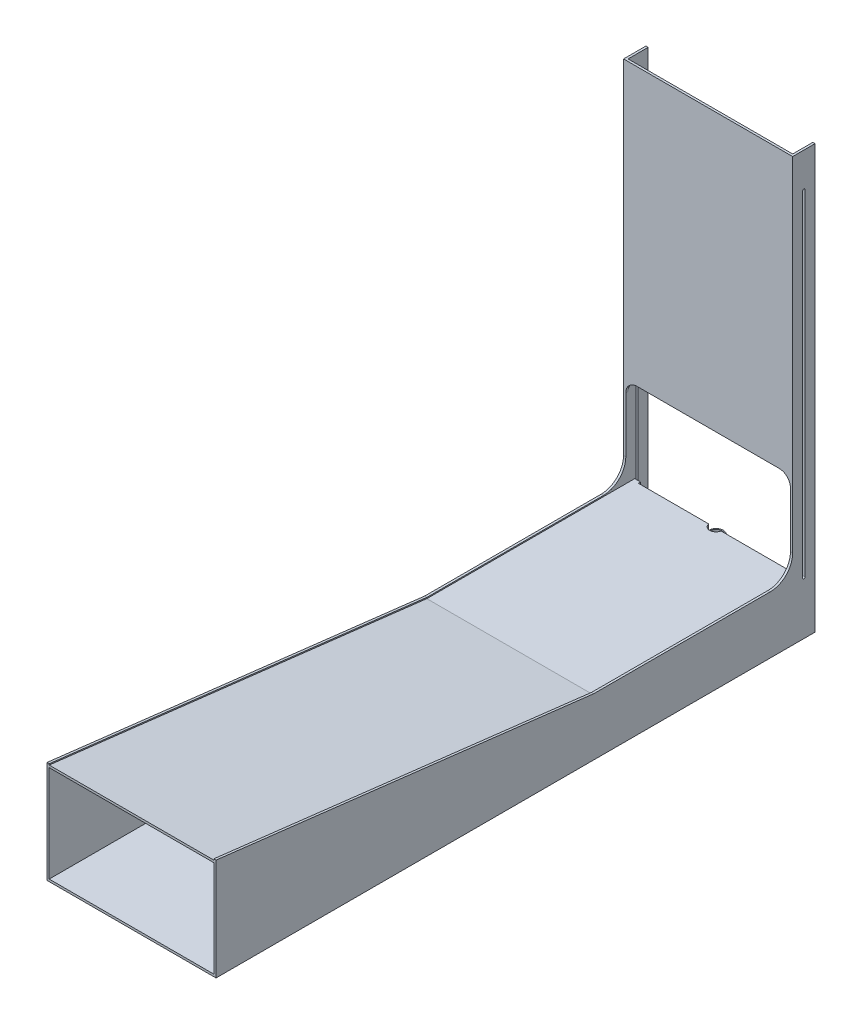
SolidWorks part; units mm, degrees
material "AISI 4340 Steel, annealed"
ref_plane "Front Plane" through (0, 0, 0) normal (0, 0, 1) x (1, 0, 0)
ref_plane "Top Plane" through (0, 0, 0) normal (0, 1, 0) x (1, 0, 0)
ref_plane "Right Plane" through (0, 0, 0) normal (1, 0, 0) x (0, 0, -1)
ref_plane "Right side of elevator platform" through (368, 0, 0) normal (1, 0, 0) x (0, 0, -1)
sketch "Sketch2" plane through (368, 0, 0) normal (1, 0, 0) x (0, 0, -1)
  line L0 (50, 236.5) -> (50, 1736.5) construction
  line L1 (45, 236.5) -> (45, 1736.5)
  line L2 (55, 236.5) -> (55, 1736.5)
  line L4 (0, 0) -> (100, 0)
  line L5 (0, 0) -> (0, 1800)
  line L6 (0, 1800) -> (100, 1800)
  line L7 (100, 0) -> (100, 1800)
  arc A0 (45, 236.5) -> (55, 236.5) centre (50, 236.5) ccw
  arc A1 (55, 1736.5) -> (45, 1736.5) centre (50, 1736.5) ccw
  point P2 (50, 986.5)
  dimension "D6" = 5
  dimension "D1" = 1800
  dimension "D2" = 100
  dimension "D3" = 50
  dimension "D4" = 236.5
  dimension "D5" = 63.5
extrude "Right side guide" add sketch "Sketch2" along normal blind 10
sketch "Sketch3" plane through (368, 0, 0) normal (-1, 0, 0) x (0, 0, 1)
  line L0 (0, 1800) -> (0, 0) construction
  line L1 (-100, 0) -> (0, 0)
  line L2 (-100, 0) -> (-100, 10)
  line L3 (-100, 10) -> (0, 10)
  line L4 (0, 0) -> (0, 10)
  dimension "D1" = 10
extrude "Bottom connection" add sketch "Sketch3" along normal blind 736
sketch "Sketch4" plane through (-368, 0, 0) normal (-1, 0, 0) x (0, 0, 1)
  line L0 (-55, 236.5) -> (-55, 1736.5) construction
  line L1 (-45, 1736.5) -> (-45, 236.5) construction
  line L2 (-55, 236.5) -> (-55, 1736.5)
  line L3 (-45, 1736.5) -> (-45, 236.5)
  line L4 (-100, 10) -> (0, 10)
  line L5 (0, 10) -> (0, 1800)
  line L6 (0, 1800) -> (-100, 1800)
  line L7 (-100, 1800) -> (-100, 10)
  line L9 (0, 10) -> (0, 1800)
  line L10 (0, 1800) -> (-100, 1800)
  line L11 (-100, 1800) -> (-100, 10)
  line L16 (-100, 10) -> (-100, 0)
  line L17 (-100, 0) -> (0, 0)
  line L18 (0, 0) -> (0, 10)
  line L19 (0, 10) -> (-100, 10)
  line L20 (-100, 10) -> (-100, 0)
  line L21 (-100, 0) -> (0, 0)
  line L22 (0, 0) -> (0, 10)
  arc A0 (-45, 1736.5) -> (-55, 1736.5) centre (-50, 1736.5) ccw construction
  arc A1 (-55, 236.5) -> (-45, 236.5) centre (-50, 236.5) ccw construction
  arc A2 (-45, 1736.5) -> (-55, 1736.5) centre (-50, 1736.5) ccw
  arc A3 (-55, 236.5) -> (-45, 236.5) centre (-50, 236.5) ccw
  dimension "D1" = 0
  dimension "D2" = 0
extrude "Left side guide" add sketch "Sketch4" along normal blind 10
sketch "Sketch5" plane through (0, 0, 0) normal (0, 0, 1) x (1, 0, 0)
  line L0 (-368, 10) -> (-368, 1800) construction
  line L1 (-368, 1800) -> (368, 1800)
  line L2 (-368, 1800) -> (-368, 653.8)
  line L3 (-368, 653.8) -> (368, 653.8)
  line L4 (368, 1800) -> (368, 653.8)
  line L5 (368, 1800) -> (368, 10) construction
  line L6 (378, 1800) -> (368, 1800) construction
  line L7 (-368, 10) -> (368, 10) construction
  dimension "D1" = 643.8
extrude "Structural webbing extrude" add sketch "Sketch5" against normal blind 10
sketch "Sketch6" plane through (0, 0, 0) normal (0, 0, 1) x (1, 0, 0)
  line L0 (-378, 251.5) -> (-378, 0)
  line L1 (-378, 0) -> (-378, 1800) construction
  line L2 (-378, 0) -> (378, 0)
  line L3 (378, 0) -> (378, 251.5)
  line L4 (378, 1800) -> (378, 0) construction
  line L5 (378, 251.5) -> (368, 251.5)
  line L6 (368, 653.8) -> (368, 10) construction
  line L7 (368, 251.5) -> (368, 10)
  line L8 (368, 10) -> (-368, 10)
  line L9 (-368, 10) -> (-368, 251.5)
  line L10 (-368, 10) -> (-368, 653.8) construction
  line L11 (-368, 251.5) -> (-378, 251.5)
  dimension "D1" = 241.5
extrude "Input roller holder extrude" add sketch "Sketch6" along normal blind 452.52
sketch "Sketch7" plane through (368, 0, 0) normal (-1, 0, 0) x (0, 0, 1)
  line L0 (0, 653.8) -> (0, 251.5) construction
  line L1 (452.52, 251.5) -> (-40, 251.5)
  line L2 (452.52, 251.5) -> (452.52, 241.5)
  line L3 (452.52, 241.5) -> (-40, 241.5)
  line L4 (-40, 251.5) -> (-40, 241.5)
  dimension "D1" = 40
  dimension "D2" = 10
extrude "Input roller platform" add sketch "Sketch7" along normal up to next
sketch "Sketch8" plane through (0, 251.5, 0) normal (0, 1, 0) x (1, 0, 0)
  line L1 (-378, -452.52) -> (-368, -452.52)
  line L2 (-378, -452.52) -> (-378, 0)
  line L3 (-378, 0) -> (-368, 0)
  line L4 (-368, -452.52) -> (-368, 0)
  line L5 (368, 0) -> (378, 0)
  line L6 (368, 0) -> (368, -452.52)
  line L7 (368, -452.52) -> (378, -452.52)
  line L8 (378, 0) -> (378, -452.52)
extrude "Siding outline" add sketch "Sketch8" along normal blind 5
sketch "Sketch9" plane through (0, 1800, 0) normal (0, 1, 0) x (1, 0, 0)
  line L8 (368, 100) -> (368, 10)
  line L9 (368, 10) -> (-368, 10)
  line L10 (-368, 10) -> (-368, 100)
  line L11 (-368, 100) -> (-378, 100)
  line L12 (-378, 100) -> (-378, 0)
  line L13 (-378, 0) -> (378, 0)
  line L14 (378, 0) -> (378, 100)
  line L15 (378, 100) -> (368, 100)
  line L16 (368, 100) -> (368, 10)
  line L17 (368, 10) -> (-368, 10)
  line L18 (-368, 10) -> (-368, 100)
  line L19 (-368, 100) -> (-378, 100)
  line L20 (-378, 100) -> (-378, 0)
  line L21 (-378, 0) -> (378, 0)
  line L22 (378, 0) -> (378, 100)
  line L23 (378, 100) -> (368, 100)
  dimension "D1" = 0
extrude "Lip to prevent box from falling out" add sketch "Sketch9" along normal blind 91.5
fillet "Vertical section fillets" radius 100 2 edges at (373, 256.5, 0) (-373, 256.5, 0)
fillet "Smaller fillets" radius 50 2 edges at (368, 653.8, -5) (-368, 653.8, -5)
sketch "Sketch11" plane through (0, 0, -40) normal (0, 0, -1) x (-1, 0, 0)
  line L0 (368, 251.5) -> (-368, 251.5) construction
  line L1 (-343, 251.5) -> (343, 251.5)
  line L2 (-343, 251.5) -> (-343, 241.5)
  line L3 (-343, 241.5) -> (343, 241.5)
  line L4 (343, 251.5) -> (343, 241.5)
  line L5 (368, 241.5) -> (-368, 241.5) construction
  line L6 (-368, 251.5) -> (-368, 241.5) construction
  line L7 (368, 251.5) -> (368, 241.5) construction
  dimension "D1" = 25
  dimension "D2" = 25
extrude "Gate spacing cut" cut sketch "Sketch11" against normal blind 10
sketch "Sketch12" plane through (-368, 0, 0) normal (1, 0, 0) x (0, 0, -1)
  line L1 (45, 221.5) -> (40, 221.5)
  line L2 (45, 221.5) -> (45, 10)
  line L3 (45, 10) -> (40, 10)
  line L4 (40, 221.5) -> (40, 10)
  line L5 (100, 1891.5) -> (100, 10) construction
  line L6 (45, 236.5) -> (45, 1736.5) construction
  line L7 (-452.52, 10) -> (100, 10) construction
  line L8 (40, 241.5) -> (-452.52, 241.5) construction
  line L9 (30, 241.5) -> (25, 241.5)
  line L10 (30, 241.5) -> (30, 10)
  line L11 (30, 10) -> (25, 10)
  line L12 (25, 241.5) -> (25, 10)
  dimension "D1" = 60
  dimension "D2" = 20
  dimension "D3" = 5
extrude "Gate guide rails" add sketch "Sketch12" along normal up to next
sketch "Sketch13" plane through (0, 0, -45) normal (0, 0, -1) x (-1, 0, 0)
  line L0 (-368, 221.5) -> (368, 221.5) construction
  line L1 (-328, 221.5) -> (328, 221.5)
  line L2 (-328, 221.5) -> (-328, 10)
  line L3 (-328, 10) -> (328, 10)
  line L4 (328, 221.5) -> (328, 10)
  line L5 (368, 10) -> (-368, 10) construction
  line L6 (-368, 10) -> (-368, 1891.5) construction
  point P8 (0, 221.5)
  dimension "D1" = 40
extrude "Gate rod connection cutout" cut sketch "Sketch13" against normal through all
sketch "Sketch14" plane through (0, 10, 0) normal (0, 1, 0) x (1, 0, 0)
  line L0 (328, 45) -> (-328, 25) construction
  circle A0 centre (0, 35) radius 28
  circle A1 centre (0, 35) radius 33
  point P7 (0, 35)
  dimension "D1" = 56
  dimension "D2" = 5
extrude "Spring cup" add sketch "Sketch14" along normal blind 75
sketch "Sketch15" plane through (0, 85, 0) normal (0, 1, 0) x (1, 0, 0)
  line L0 (368, 30) -> (328, 30) construction
  line L1 (32.619, 30) -> (27.55, 30)
  line L3 (32.619, 40) -> (27.55, 40)
  line L5 (-27.55, 40) -> (-32.619, 40)
  line L6 (-27.55, 30) -> (-32.619, 30)
  circle A0 centre (0, 35) radius 28 construction
  arc A1 (27.55, 40) -> (-27.55, 40) centre (0, 35) ccw
  circle A2 centre (0, 35) radius 33 construction
  arc A3 (32.619, 40) -> (-32.619, 40) centre (0, 35) ccw
  arc A4 (-27.55, 30) -> (27.55, 30) centre (0, 35) ccw
  arc A5 (-32.619, 30) -> (32.619, 30) centre (0, 35) ccw
extrude "Spring container extension" add sketch "Sketch15" along normal up to surface (136.5 mm away) up to face at (0, 221.5, -27.5)
sketch "Sketch16" plane through (0, 221.5, 0) normal (0, 1, 0) x (1, 0, 0)
  circle A0 centre (0, 35) radius 28
  arc A1 (27.55, 40) -> (-27.55, 40) centre (0, 35) ccw construction
extrude "Spring hole (can't insert spring without this)" cut sketch "Sketch16" along normal up to surface (30 mm away) up to face at (0, 251.5, 85.63)
sketch "Sketch17" plane through (0, 221.5, 0) normal (0, 1, 0) x (1, 0, 0)
  line L2 (-26.1534, 25) -> (-31.4484, 25)
  line L3 (31.4484, 25) -> (26.1534, 25)
  line L4 (-26.1534, 25) -> (-31.4484, 25)
  line L5 (31.4484, 25) -> (26.1534, 25)
  arc A2 (-31.4484, 25) -> (31.4484, 25) centre (0, 35) ccw
  arc A3 (-26.1534, 25) -> (26.1534, 25) centre (0, 35) ccw
  arc A4 (-31.4484, 25) -> (31.4484, 25) centre (0, 35) ccw
  arc A5 (-26.1534, 25) -> (26.1534, 25) centre (0, 35) ccw
  dimension "D1" = 0
extrude "Container extension to meet with conveyor plate" add sketch "Sketch17" along normal up to next
fillet "Spring holder fillets" radius 10 4 edges at (0, 10, -68) (-31.4484, 231.5, -25) (31.4484, 231.5, -25) (0, 241.5, -2)
sketch "Sketch18" plane through (0, 0, 452.52) normal (0, 0, 1) x (1, 0, 0)
  line L0 (368, 10) -> (368, 241.5) construction
  line L1 (-368, 241.5) -> (-368, 10) construction
  line L2 (368, 10) -> (368, 241.5)
  line L3 (-368, 241.5) -> (-368, 10)
  line L4 (-368, 241.5) -> (368, 241.5)
  line L5 (368, 10) -> (-368, 10)
  line L8 (378, 0) -> (378, 256.5)
  line L9 (378, 256.5) -> (368, 256.5)
  line L10 (368, 256.5) -> (368, 251.5)
  line L11 (368, 251.5) -> (-368, 251.5)
  line L12 (-368, 251.5) -> (-368, 256.5)
  line L13 (-368, 256.5) -> (-378, 256.5)
  line L14 (-378, 256.5) -> (-378, 0)
  line L15 (-378, 0) -> (378, 0)
  line L16 (378, 0) -> (378, 256.5)
  line L17 (378, 256.5) -> (368, 256.5)
  line L18 (368, 256.5) -> (368, 251.5)
  line L19 (368, 251.5) -> (-368, 251.5)
  line L20 (-368, 251.5) -> (-368, 256.5)
  line L21 (-368, 256.5) -> (-378, 256.5)
  line L22 (-378, 256.5) -> (-378, 0)
  line L23 (-378, 0) -> (378, 0)
  dimension "D1" = 0
extrude "Extension to fit with sorter loop exit stuff" add sketch "Sketch18" along normal blind 437
sketch "Sketch19" plane through (-378, 0, 0) normal (-1, 0, 0) x (0, 0, 1)
  line L0 (889.52, 251.5) -> (2577.86, 451.5)
  line L1 (2577.86, 451.5) -> (2577.86, 441.5)
  line L2 (2577.86, 441.5) -> (889.52, 241.5)
  line L3 (889.52, 256.5) -> (889.52, 0) construction
  line L4 (889.52, 241.5) -> (889.52, 251.5)
  line L6 (889.52, 0) -> (2577.86, 0)
  line L7 (889.52, 0) -> (889.52, 10)
  line L8 (889.52, 10) -> (2577.86, 10)
  line L9 (2577.86, 0) -> (2577.86, 10)
  dimension "D1" = 1688.34
  dimension "D2" = 200
extrude "Horizontal plates (extension to output from sorter)" add sketch "Sketch19" against normal up to surface (756 mm away) up to face at (378, 661.6842, 236.9042)
sketch "Sketch20" plane through (0, 0, 0) normal (0, -1, 0) x (1, 0, 0)
  line L0 (0, -544.236) -> (0, 544.236) construction
  line L1 (-378, 2577.86) -> (-368, 2577.86)
  line L2 (-378, 2577.86) -> (-378, 889.52)
  line L3 (-378, 889.52) -> (-368, 889.52)
  line L4 (-368, 2577.86) -> (-368, 889.52)
  line L9 (368, 2577.86) -> (368, 889.52)
  line L10 (378, 889.52) -> (368, 889.52)
  line L11 (378, 2577.86) -> (378, 889.52)
  line L12 (378, 2577.86) -> (368, 2577.86)
  dimension "D1" = 10
extrude "Vertical plates (extension to output from sorter)" add sketch "Sketch20" against normal offset from surface (456.535 mm away) 5 up to face at (0, 318.1667, 1452.3) offset beyond the face yes
